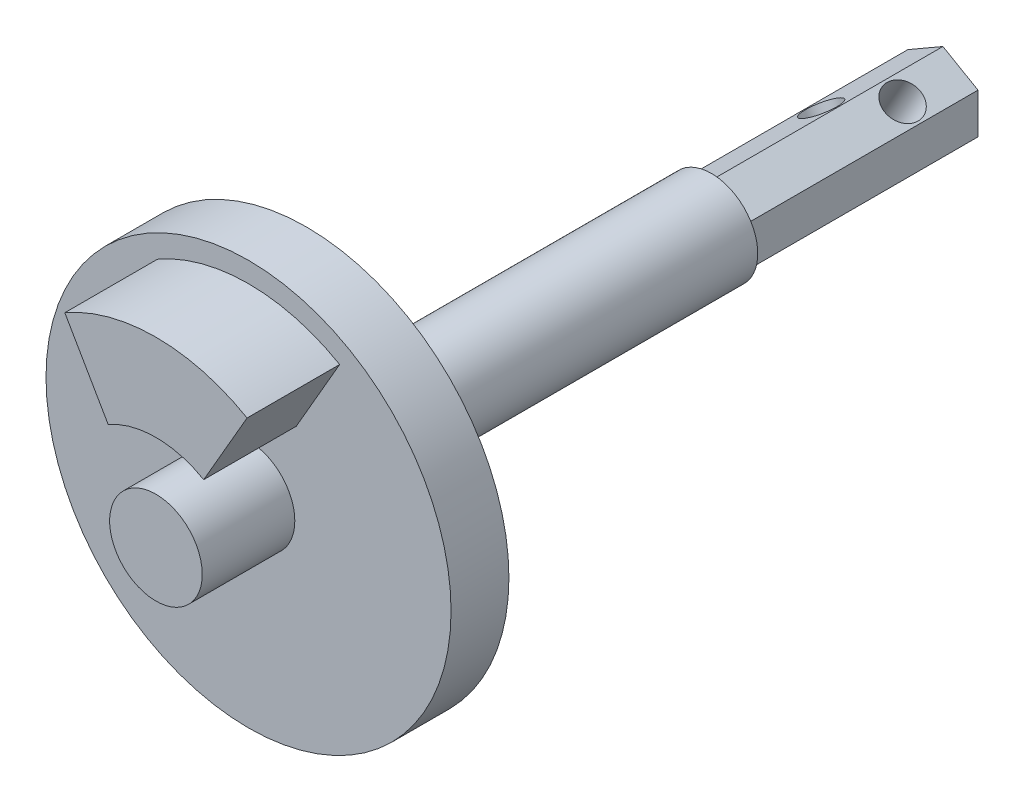
SolidWorks part; units mm, degrees
ref_plane "Front Plane" through (0, 0, 0) normal (0, 0, 1) x (1, 0, 0)
ref_plane "Top Plane" through (0, 0, 0) normal (0, 1, 0) x (1, 0, 0)
ref_plane "Right Plane" through (0, 0, 0) normal (1, 0, 0) x (0, 0, -1)
sketch "Sketch1" plane through (0, 0, 0) normal (0, 0, 1) x (1, 0, 0)
  circle A0 centre (0, 0) radius 17.5
  dimension "D1" = 35
extrude "Boss-Extrude1" add sketch "Sketch1" along normal mid plane 5
sketch "Sketch2" plane through (0, 0, 2.5) normal (0, 0, 1) x (1, 0, 0)
  line L3 (0, 0) -> (0, 11) construction
  line L4 (7.875, 13.6399) -> (4.125, 7.1447)
  line L5 (-4.125, 7.1447) -> (-7.875, 13.6399)
  arc A1 (4.125, 7.1447) -> (-4.125, 7.1447) centre (0, 0) ccw
  arc A6 (-7.875, 13.6399) -> (7.875, 13.6399) centre (0, 0) cw
  circle A7 centre (0, 0) radius 17.5 construction
  dimension "D2" = 7.5
  dimension "D3" = 1.75
  dimension "D1" = 30
extrude "Boss-Extrude2" add sketch "Sketch2" along normal blind 8
sketch "Sketch3" plane through (0, 0, 2.5) normal (0, 0, 1) x (1, 0, 0)
  circle A0 centre (0, 0) radius 4
extrude "Boss-Extrude3" add sketch "Sketch3" along normal blind 8
sketch "Sketch7" plane through (0, 0, -2.5) normal (0, 0, -1) x (-1, 0, 0)
  circle A0 centre (0, 0) radius 4
extrude "Boss-Extrude4" add sketch "Sketch7" along normal blind 35
sketch "Sketch9" plane through (0, 0, -37.5) normal (0, 0, -1) x (-1, 0, 0)
  line L11 (0, 3.5) -> (-3.0311, 1.75)
  line L12 (-3.0311, 1.75) -> (-3.0311, -1.75)
  line L13 (-3.0311, -1.75) -> (0, -3.5)
  line L14 (0, -3.5) -> (3.0311, -1.75)
  line L15 (3.0311, -1.75) -> (3.0311, 1.75)
  line L16 (3.0311, 1.75) -> (0, 3.5)
  point P5 (0, 0)
  point P6 (0, 0)
  point P8 (0, 0)
  point P11 (0, 0)
  point P13 (0, 0)
  point P15 (0, 0)
extrude "Boss-Extrude5" add sketch "Sketch9" along normal blind 20
sketch "Sketch10" plane through (-1.5155, -2.625, 0) normal (-0.5, -0.866, 0) x (0.866, -0.5, 0)
  line L2 (0, -52.5) -> (0, -37.5) construction
  line L3 (1.75, -37.5) -> (-1.75, -37.5) construction
  circle A0 centre (0, -52.5) radius 1.55
extrude "Cut-Extrude1" cut sketch "Sketch10" against normal blind 6.1
sketch "Sketch11" plane through (1.5155, -2.625, 0) normal (-0.5, 0.866, 0) x (0, 0, 1)
  line L0 (-48.5, 0) -> (-37.5, 0) construction
  line L1 (-37.5, 1.75) -> (-37.5, -1.75) construction
  circle A1 centre (-48.5, 0) radius 1.55
extrude "Cut-Extrude4" cut sketch "Sketch11" along normal blind 6.1
